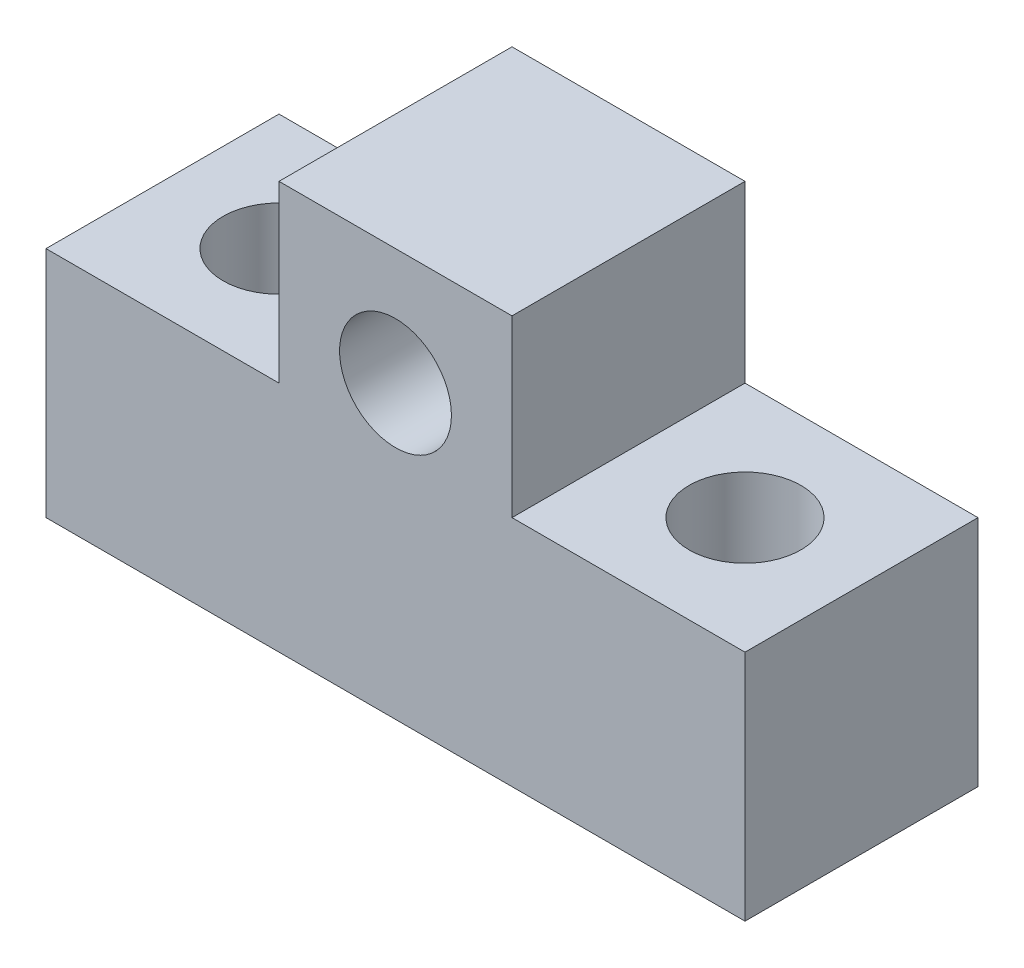
SolidWorks part; units mm, degrees
ref_plane "Front Plane" through (0, 0, 0) normal (0, 0, 1) x (1, 0, 0)
ref_plane "Top Plane" through (0, 0, 0) normal (0, 1, 0) x (1, 0, 0)
ref_plane "Right Plane" through (0, 0, 0) normal (1, 0, 0) x (0, 0, -1)
sketch "Sketch1" plane through (0, 0, 0) normal (0, 0, 1) x (1, 0, 0)
  line L0 (-9.525, 3.175) -> (9.525, -3.175) construction
  line L1 (-9.525, 3.175) -> (9.525, 3.175)
  line L2 (-9.525, 3.175) -> (-9.525, -3.175)
  line L3 (-9.525, -3.175) -> (9.525, -3.175)
  line L4 (9.525, 3.175) -> (9.525, -3.175)
  point P4 (0, 0)
  dimension "D1" = 19.05
  dimension "D2" = 6.35
extrude "Boss-Extrude1" add sketch "Sketch1" along normal blind 6.35
sketch "Sketch6" plane through (0, 3.175, 0) normal (0, 1, 0) x (1, 0, 0)
  line L0 (9.525, 0) -> (-9.525, 0) construction
  line L1 (3.175, 0) -> (-3.175, 0)
  line L2 (3.175, 0) -> (3.175, -6.35)
  line L3 (3.175, -6.35) -> (-3.175, -6.35)
  line L4 (-3.175, 0) -> (-3.175, -6.35)
  line L5 (9.525, -6.35) -> (-9.525, -6.35) construction
  point P8 (0, 0)
  point P9 (0, 0)
  dimension "D1" = 6.35
extrude "Boss-Extrude2" add sketch "Sketch6" along normal blind 4.7625
hole_wizard "Tapped Hole for #4-40 Helicoil1" positions "Sketch2" profile "Sketch3" tap size "#4-40" standard "Helicoil® Inch" end condition through all
sketch "Sketch2" plane through (0, 3.175, 0) normal (0, 1, 0) x (1, 0, 0)
  line L0 (0, 0) -> (0, -6.35) construction
  line L4 (-9.525, -6.35) -> (-9.525, 0) construction
  line L5 (-9.525, -6.35) -> (9.525, -6.35) construction
  line L6 (-9.525, 0) -> (9.525, 0) construction
  point P0 (-6.35, -3.175)
  point P13 (6.35, -3.175)
  point P16 (0, -3.175)
  dimension "D1" = 3.175
sketch "Sketch3" plane through (-6.35, 3.175, 3.175) normal (1, 0, 0) x (0, 0, 1)
  line L0 (0, 0) -> (0, 6.35)
  line L1 (0, 6.35) -> (1.524, 6.35)
  line L2 (1.524, 6.35) -> (1.524, 0)
  line L5 (1.524, 0) -> (0, 0)
  line L11 (0, -6.35) -> (0, 107.95) construction
  dimension "Thru Tap Drill Dia." = 3.048
  dimension "Thru Tap Drill Depth" = 6.35
cosmetic thread "Hole Thread1" parameters "D1"=3.556, "D2"=3.7414
cosmetic thread "Hole Thread2" parameters "D1"=3.556, "D2"=3.7414
hole_wizard "Tapped Hole for #4-40 Helicoil2" positions "Sketch4" profile "Sketch5" tap size "#4-40" standard "Helicoil® Inch" end condition through all
sketch "Sketch4" plane through (0, 0, 6.35) normal (0, 0, 1) x (1, 0, 0)
  line L6 (-3.175, 4.7625) -> (0, 4.7625) construction
  line L7 (-3.175, 7.9375) -> (-3.175, 3.175) construction
  line L8 (0, 4.7625) -> (0, 7.9375) construction
  line L9 (-3.175, 7.9375) -> (3.175, 7.9375) construction
  point P0 (0, 4.7625)
sketch "Sketch5" plane through (0, 4.7625, 6.35) normal (1, 0, 0) x (0, -1, 0)
  line L0 (0, 0) -> (0, 6.35)
  line L1 (0, 6.35) -> (1.524, 6.35)
  line L2 (1.524, 6.35) -> (1.524, 0)
  line L5 (1.524, 0) -> (0, 0)
  line L11 (0, -6.35) -> (0, 107.95) construction
  dimension "Thru Tap Drill Dia." = 3.048
  dimension "Thru Tap Drill Depth" = 6.35
cosmetic thread "Hole Thread3" parameters "D1"=3.556, "D2"=3.7414
